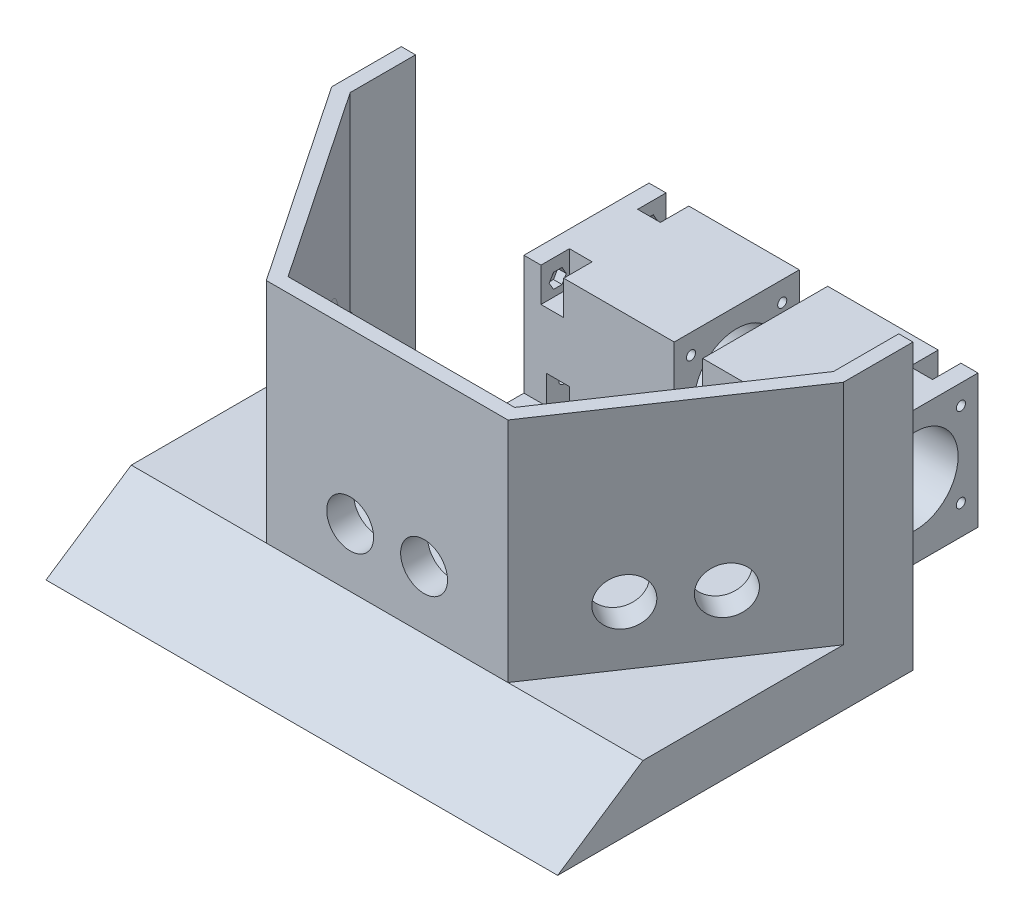
SolidWorks part; units mm, degrees
other "Markup1"
sketch "Sketch35"
ref_plane "Front Plane" through (0, 0, 0) normal (0, 0, 1) x (1, 0, 0)
ref_plane "Top Plane" through (0, 0, 0) normal (0, 1, 0) x (1, 0, 0)
ref_plane "Right Plane" through (0, 0, 0) normal (1, 0, 0) x (0, 0, -1)
sketch "Sketch1" plane through (0, 0, 0) normal (0, 0, 1) x (1, 0, 0)
  line L1 (-76.9072, 53.1245) -> (103.0928, 53.1245)
  line L2 (-76.9072, 53.1245) -> (-76.9072, -46.8755)
  line L3 (-76.9072, -46.8755) -> (103.0928, -46.8755)
  line L4 (103.0928, 53.1245) -> (103.0928, -46.8755)
  dimension "D1" = 180
  dimension "D2" = 100
extrude "Boss-Extrude1" add sketch "Sketch1" along normal blind 150
sketch "Sketch2" plane through (0, 53.1245, 0) normal (0, 1, 0) x (1, 0, 0)
  line L0 (13.0928, 0) -> (13.0928, -150) construction
  line L4 (103.0928, 0) -> (-76.9072, 0) construction
  line L9 (103.0928, -150) -> (-76.9072, -150) construction
sketch "Sketch4" plane through (0, 53.1245, 0) normal (0, 1, 0) x (1, 0, 0)
  line L0 (-29.4072, -150) -> (55.5928, -150) construction
  line L1 (-76.9072, 0) -> (-76.9072, -79.5106) construction
  line L3 (-76.9072, -150) -> (-76.9072, 0) construction
  line L5 (-76.9072, -79.5106) -> (-29.4072, -150) construction
  line L6 (13.0928, 0) -> (13.0928, -150) construction
  line L8 (103.0928, -150) -> (-76.9072, -150) construction
  line L9 (103.0928, 0) -> (103.0928, -79.5106) construction
  line L10 (103.0928, -150) -> (103.0928, 0) construction
  line L11 (103.0928, -79.5106) -> (55.5928, -150) construction
  line L13 (-76.9072, -79.5106) -> (-29.4072, -150)
  line L14 (-29.4072, -150) -> (-76.9072, -150)
  line L15 (-76.9072, -150) -> (-76.9072, -79.5106)
  line L16 (55.5928, -150) -> (103.0928, -150)
  line L17 (103.0928, -150) -> (103.0928, -79.5106)
  line L18 (103.0928, -79.5106) -> (55.5928, -150)
  line M6 (-76.9072, 0) -> (-76.9072, -150)
  line M7 (-76.9072, -150) -> (103.0928, -150)
  line M8 (103.0928, -150) -> (103.0928, 0)
  dimension "D1" = 85
  dimension "D2" = 47.5
  dimension "D3" = 47.5
  dimension "D4" = 85
  dimension "D5" = 79.5106
extrude "Cut-Extrude2" cut sketch "Sketch4" against normal blind 80 contours M8 M7 | M6 M7 region at (87.2595, 53.1245, 126.5035) region at (-61.0739, 53.1245, 126.5035)
shell "Shell1" thickness 5 removed face at (13.0928, 53.1245, 76.5035)
sketch "Sketch6" plane through (103.0928, 0, 0) normal (1, 0, 0) x (0, 0, -1)
  line L0 (-150, -26.8755) -> (-150, -46.8755)
  line L1 (-150, -46.8755) -> (-180, -46.8755)
  line L2 (-180, -46.8755) -> (-150, -26.8755)
  dimension "D1" = 30
  dimension "D2" = 36.0555
extrude "Boss-Extrude2" add sketch "Sketch6" against normal blind 180 contours L2 L0 L1
sketch "Sketch26" plane through (0, 0, 0) normal (0, 0, -1) x (-1, 0, 0)
  line L0 (76.9072, 53.1245) -> (76.9072, -46.8755) construction
  line L1 (-103.0928, 53.1245) -> (76.9072, 53.1245)
  line L2 (-103.0928, 53.1245) -> (-103.0928, -41.8755)
  line L3 (-103.0928, -41.8755) -> (76.9072, -41.8755)
  line L4 (76.9072, 53.1245) -> (76.9072, -41.8755)
  dimension "D1" = 95
extrude "Cut-Extrude10" cut sketch "Sketch26" against normal blind 5
sketch "Sketch27" plane through (103.0928, 0, 0) normal (1, 0, 0) x (0, 0, -1)
  line L1 (-5, 53.1245) -> (-55, 53.1245)
  line L2 (-5, 53.1245) -> (-5, -41.8755)
  line L3 (-5, -41.8755) -> (-55, -41.8755)
  line L4 (-55, 53.1245) -> (-55, -41.8755)
  dimension "D1" = 50
  dimension "D2" = 95
extrude "Cut-Extrude11" cut sketch "Sketch27" against normal through all
sketch3d "3DSketch1" plane through (0, 0, 0) normal (0, 0, 1) x (1, 0, 0)
sketch "Sketch28" plane through (-89.7376, 0, 60.4706) normal (-0.8293, 0, 0.5588) x (0.5588, 0, 0.8293)
  line L0 (22.9595, -26.8755) -> (107.9595, -26.8755) construction
  line L1 (107.9595, -26.8755) -> (107.9595, 53.1245) construction
  line L2 (22.9595, -26.8755) -> (22.9595, 53.1245) construction
  circle A0 centre (52.4595, -6.2755) radius 8.25
  circle A1 centre (78.4595, -6.2755) radius 8.25
  dimension "D1" = 16.5
  dimension "D2" = 16.5
  dimension "D3" = 26
  dimension "D4" = 20.6
  dimension "D5" = 29.5
  dimension "D6" = 29.5
extrude "Cut-Extrude12" cut sketch "Sketch28" against normal blind 82
sketch "Sketch29" plane through (107.7458, 0, 72.6056) normal (0.8293, 0, 0.5588) x (0.5588, 0, -0.8293)
  line L0 (-8.3264, -26.8755) -> (-8.3264, 53.1245) construction
  line L2 (-8.3264, -26.8755) -> (-93.3264, -26.8755) construction
  circle A0 centre (-63.8264, -6.2755) radius 8.25
  circle A1 centre (-37.8264, -6.2755) radius 8.25
  dimension "D1" = 16.5
  dimension "D2" = 16.5
  dimension "D3" = 26
  dimension "D4" = 29.5
  dimension "D5" = 20.6
  dimension "D6" = 20.6
extrude "Cut-Extrude13" cut sketch "Sketch29" against normal blind 82
sketch "Sketch30" plane through (0, 0, 150) normal (0, 0, 1) x (1, 0, 0)
  line L0 (-29.4072, -26.8755) -> (55.5928, -26.8755) construction
  line L1 (55.5928, -26.8755) -> (55.5928, 53.1245) construction
  line L2 (-29.4072, -26.8755) -> (-29.4072, 53.1245) construction
  circle A0 centre (0.0928, -6.2755) radius 8.25
  circle A1 centre (26.0928, -6.2755) radius 8.25
  dimension "D1" = 16.5
  dimension "D2" = 16.5
  dimension "D4" = 20.6
  dimension "D3" = 26
  dimension "D5" = 20.6
  dimension "D6" = 29.5
  dimension "D7" = 29.5
extrude "Cut-Extrude14" cut sketch "Sketch30" against normal blind 82 contours A0 | A1
sketch "Sketch31" plane through (103.5994, 0, 69.8115) normal (-0.8293, 0, -0.5588) x (-0.5588, 0, 0.8293)
  circle A1 centre (63.8264, -6.2755) radius 10.25
  circle A2 centre (63.8264, -6.2755) radius 8.25 construction
  circle A3 centre (37.8264, -6.2755) radius 10.25
  circle A4 centre (37.8264, -6.2755) radius 8.25 construction
  circle A5 centre (63.8264, -6.2755) radius 8.25
  circle A6 centre (37.8264, -6.2755) radius 8.25
  dimension "D1" = 2
  dimension "D2" = 2
extrude "Boss-Extrude4" add sketch "Sketch31" along normal blind 4.5
sketch "Sketch33" plane through (0, 0, 145) normal (0, 0, -1) x (-1, 0, 0)
  circle A0 centre (-26.0928, -6.2755) radius 8.25
  circle A1 centre (-26.0928, -6.2755) radius 10.25
  circle A2 centre (-0.0928, -6.2755) radius 8.25
  circle A3 centre (-0.0928, -6.2755) radius 10.25
  dimension "D1" = 2
  dimension "D2" = 2
extrude "Boss-Extrude5" add sketch "Sketch33" along normal blind 4.5
sketch "Sketch34" plane through (-85.5911, 0, 57.6765) normal (0.8293, 0, -0.5588) x (-0.5588, 0, -0.8293)
  circle A0 centre (-78.4595, -6.2755) radius 8.25
  circle A1 centre (-52.4595, -6.2755) radius 8.25
  circle A2 centre (-78.4595, -6.2755) radius 10.25
  circle A3 centre (-52.4595, -6.2755) radius 10.25
  dimension "D1" = 2
  dimension "D2" = 2
extrude "Boss-Extrude6" add sketch "Sketch34" along normal blind 4.5
fillet "Fillet1" radius 3 6 edges at (-50.5475, -6.2755, 109.6807) (-36.0181, -6.2755, 131.2421) (10.3428, -6.2755, 145) (36.3428, -6.2755, 145) (76.7331, -6.2755, 109.6807) (62.2037, -6.2755, 131.2421)
sketch "Sketch68" plane through (0, -41.8755, 0) normal (0, 1, 0) x (1, 0, 0)
  line L0 (-54.5072, -131.3) -> (-61.9072, -138.7) construction
  line L1 (-61.9072, -131.3) -> (-54.5072, -131.3)
  line L2 (-61.9072, -131.3) -> (-61.9072, -138.7)
  line L3 (-61.9072, -138.7) -> (-54.5072, -138.7)
  line L4 (-54.5072, -131.3) -> (-54.5072, -138.7)
  line L5 (-76.9072, -180) -> (103.0928, -180) construction
  line L6 (-76.9072, -180) -> (-76.9072, 0) construction
  line L7 (13.0928, -145) -> (13.0928, -117.6017) construction
  line L8 (-71.9072, -145) -> (98.0928, -145) construction
  line L9 (13.0928, 0) -> (13.0928, -150) construction
  line L10 (80.6928, -131.3) -> (88.0928, -138.7) construction
  line L11 (80.6928, -131.3) -> (80.6928, -138.7)
  line L12 (88.0928, -138.7) -> (80.6928, -138.7)
  line L13 (88.0928, -131.3) -> (88.0928, -138.7)
  line L14 (88.0928, -131.3) -> (80.6928, -131.3)
  point P4 (-58.2072, -135)
  dimension "D1" = 7.4
  dimension "D2" = 7.4
  dimension "D3" = 45
  dimension "D4" = 15
extrude "Cut-Extrude40" cut sketch "Sketch68" against normal blind 26
sketch "Sketch69" plane through (0, -41.8755, 0) normal (0, 1, 0) x (1, 0, 0)
  line L0 (-58.2072, -131.3) -> (-58.2072, -123.2) construction
  line L1 (-54.5072, -131.3) -> (-61.9072, -131.3) construction
  line L2 (13.0928, -180) -> (13.0928, -157.8617) construction
  line L3 (-76.9072, -180) -> (103.0928, -180) construction
  line L4 (84.3928, -131.3) -> (84.3928, -123.2) construction
  circle A0 centre (-58.2072, -123.2) radius 1.65
  circle A1 centre (84.3928, -123.2) radius 1.65
  dimension "D1" = 3.3
  dimension "D2" = 8.1
extrude "Cut-Extrude41" cut sketch "Sketch69" against normal blind 26
sketch "Sketch70" plane through (0, -46.8755, 0) normal (0, -1, 0) x (1, 0, 0)
  circle A0 centre (84.3928, 123.2) radius 4
  circle A1 centre (-58.2072, 123.2) radius 4
  dimension "D1" = 8
  dimension "D2" = 8
extrude "Cut-Extrude43" cut sketch "Sketch70" against normal blind 3
sketch "Sketch36" plane through (0, -41.8755, 0) normal (0, 1, 0) x (1, 0, 0)
  line L0 (13.0928, 0) -> (8.0928, 0) construction
  line L1 (103.0928, 0) -> (-76.9072, 0) construction
  line L2 (13.0928, 0) -> (18.0928, 0) construction
  line L3 (13.0928, -150) -> (13.0928, -80.1183) construction
  line L8 (13.0928, 0) -> (13.0928, -150) construction
  line L9 (18.0928, 0) -> (70.9628, 0) construction
  line L14 (8.0928, -44) -> (-44.7772, -44)
  line L15 (18.0928, 0) -> (70.9628, 0)
  line L16 (18.0928, 0) -> (18.0928, -44)
  line L17 (18.0928, -44) -> (70.9628, -44)
  line L18 (70.9628, 0) -> (70.9628, -44)
  line L19 (-44.7772, 0) -> (-44.7772, -44)
  line L20 (8.0928, 0) -> (-44.7772, 0)
  line L21 (8.0928, 0) -> (8.0928, -44)
  dimension "D1" = 44
  dimension "D2" = 5
  dimension "D5" = 52.87
extrude "Boss-Extrude7" add sketch "Sketch36" along normal blind 42 contours L17 L18 L15 L16 | L14 L19 L20 L21
sketch "Sketch72" plane through (0, -41.8755, 0) normal (0, 1, 0) x (1, 0, 0)
  line L0 (13.0928, -150) -> (13.0928, -110.5101) construction
  line L1 (103.0928, -55) -> (70.9628, -55)
  line L2 (103.0928, -55) -> (103.0928, 0)
  line L3 (103.0928, 0) -> (70.9628, 0)
  line L4 (70.9628, -55) -> (70.9628, 0)
  line L5 (13.0928, 0) -> (13.0928, -150) construction
  line L6 (-76.9072, 0) -> (-44.7772, 0)
  line L7 (-44.7772, -55) -> (-44.7772, 0)
  line L8 (-76.9072, -55) -> (-44.7772, -55)
  line L9 (-76.9072, -55) -> (-76.9072, 0)
  line M12 (-44.7772, -44) -> (-44.7772, 0)
  line M13 (-44.7772, 0) -> (-76.9072, 0)
  line M14 (-76.9072, 0) -> (-76.9072, -55)
  line M15 (-76.9072, -55) -> (-71.9072, -55)
extrude "Cut-Extrude44" cut sketch "Sketch72" against normal blind 42 contours L8 L7 M15 M12 M13 M14 | L2 L1 L4 L3 region at (-60.8422, -41.8755, 27.5)
sketch "Sketch73" plane through (70.9628, 0, 0) normal (1, 0, 0) x (0, 0, -1)
  line L0 (-42.1, -1.6755) -> (-1.9, -1.6755) construction
  line L1 (-1.9, -1.6755) -> (-1.9, -41.8755) construction
  line L2 (-1.9, -41.8755) -> (-42.1, -41.8755) construction
  line L3 (-42.1, -41.8755) -> (-42.1, -1.6755) construction
  line L4 (0, 0.1245) -> (0, -46.8755) construction
  line L5 (-44, 0.1245) -> (-44, -41.8755) construction
  line L6 (-42.1, -21.7755) -> (-1.9, -21.7755) construction
  line L7 (-22, -41.8755) -> (-22, -1.6755) construction
  line L9 (-55, -46.8755) -> (0, -46.8755) construction
  circle A0 centre (-38.1, -6.8755) radius 1.6
  circle A4 centre (-6, -6.8755) radius 1.6
  circle A5 centre (-38.1, -36.4755) radius 1.6
  circle A7 centre (-6.05, -36.4755) radius 1.6
  circle A8 centre (-22, -21.7755) radius 15
  dimension "D5" = 3.2
  dimension "D8" = 3.2
  dimension "D11" = 3.2
  dimension "D12" = 3.2
  dimension "D17" = 30
  dimension "D1" = 40.2
  dimension "D2" = 1.9
  dimension "D3" = 1.9
  dimension "D4" = 5
  dimension "D6" = 5.2
  dimension "D7" = 4
  dimension "D9" = 5.2
  dimension "D10" = 4.1
  dimension "D13" = 5.4
  dimension "D14" = 4
  dimension "D15" = 5.4
  dimension "D16" = 4.15
extrude "Cut-Extrude45" cut sketch "Sketch73" against normal blind 149 contours A4 | A5 | A7 | A0 | A8 region at (70.9628, -6.8755, 6) region at (70.9628, -36.4755, 38.1)
sketch "Sketch77" plane through (0, 0.1245, 0) normal (0, 1, 0) x (1, 0, 0)
  line L0 (18.0928, -44) -> (70.9628, -44) construction
  line L1 (64.9628, -44) -> (56.9628, -44)
  line L2 (64.9628, -44) -> (64.9628, -34)
  line L3 (64.9628, -34) -> (56.9628, -34)
  line L4 (56.9628, -44) -> (56.9628, -34)
  line L10 (18.0928, 0) -> (70.9628, 0) construction
  line L16 (56.9628, 0) -> (64.9628, 0)
  line L17 (56.9628, 0) -> (56.9628, -10)
  line L18 (56.9628, -10) -> (64.9628, -10)
  line L19 (64.9628, 0) -> (64.9628, -10)
  line L20 (70.9628, 0) -> (70.9628, -44) construction
  line L21 (13.0928, 0) -> (13.0928, -65.0172) construction
  line L22 (13.0928, 0) -> (13.0928, -150) construction
  line L23 (-30.7772, -10) -> (-38.7772, -10)
  line L24 (-38.7772, 0) -> (-38.7772, -10)
  line L25 (-30.7772, 0) -> (-38.7772, 0)
  line L26 (-30.7772, 0) -> (-30.7772, -10)
  line L27 (-38.7772, -34) -> (-30.7772, -34)
  line L28 (-30.7772, -44) -> (-30.7772, -34)
  line L29 (-38.7772, -44) -> (-30.7772, -44)
  line L30 (-38.7772, -44) -> (-38.7772, -34)
  dimension "D1" = 10
  dimension "D2" = 6
  dimension "D3" = 10
  dimension "D4" = 6
  dimension "D7" = 8
  dimension "D8" = 8
extrude "Cut-Extrude46" cut sketch "Sketch77" against normal blind 12
sketch "Sketch78" plane through (0, -46.8755, 0) normal (0, -1, 0) x (1, 0, 0)
  line L0 (70.9628, 0) -> (70.9628, 44.078) construction
  line L2 (70.9628, 55) -> (70.9628, 0) construction
  dimension "D1" = 44.078
sketch "Sketch80" plane through (64.9628, 0, 0) normal (-1, 0, 0) x (0, 0, 1)
  line L0 (10, -11.8755) -> (0, -11.8755) construction
  line L7 (4.6725, -4.1778) -> (3, -6.6763)
  line L8 (3, -6.6763) -> (4.3275, -9.374)
  line L9 (4.3275, -9.374) -> (7.3275, -9.5732)
  line L10 (7.3275, -9.5732) -> (9, -7.0747)
  line L11 (9, -7.0747) -> (7.6725, -4.3771)
  line L12 (7.6725, -4.3771) -> (4.6725, -4.1778)
  circle A0 centre (6, -6.8755) radius 2.6038 construction
  dimension "D3" = 5.2076
  dimension "D1" = 6
  dimension "D2" = 5
extrude "Cut-Extrude47" cut sketch "Sketch80" against normal blind 3
sketch "Sketch81" plane through (64.9628, 0, 0) normal (-1, 0, 0) x (0, 0, 1)
  line L1 (41.1, -6.8755) -> (39.6, -4.2774)
  line L2 (39.6, -4.2774) -> (36.6, -4.2774)
  line L3 (36.6, -4.2774) -> (35.1, -6.8755)
  line L4 (35.1, -6.8755) -> (36.6, -9.4736)
  line L5 (36.6, -9.4736) -> (39.6, -9.4736)
  line L6 (39.6, -9.4736) -> (41.1, -6.8755)
  circle A0 centre (38.1, -6.8755) radius 2.5981 construction
  dimension "D2" = 5.1962
  dimension "D1" = 6
extrude "Cut-Extrude48" cut sketch "Sketch81" against normal blind 3
sketch "Sketch82" plane through (-38.7772, 0, 0) normal (1, 0, 0) x (0, 0, -1)
  line L1 (-3, -6.8755) -> (-4.5, -4.2774)
  line L2 (-4.5, -4.2774) -> (-7.5, -4.2774)
  line L3 (-7.5, -4.2774) -> (-9, -6.8755)
  line L4 (-9, -6.8755) -> (-7.5, -9.4736)
  line L5 (-7.5, -9.4736) -> (-4.5, -9.4736)
  line L6 (-4.5, -9.4736) -> (-3, -6.8755)
  circle A0 centre (-6, -6.8755) radius 2.5981 construction
  dimension "D1" = 6
extrude "Cut-Extrude49" cut sketch "Sketch82" against normal blind 3
sketch "Sketch83" plane through (-38.7772, 0, 0) normal (1, 0, 0) x (0, 0, -1)
  line L1 (-35.1, -6.8755) -> (-36.6, -4.2774)
  line L2 (-36.6, -4.2774) -> (-39.6, -4.2774)
  line L3 (-39.6, -4.2774) -> (-41.1, -6.8755)
  line L4 (-41.1, -6.8755) -> (-39.6, -9.4736)
  line L5 (-39.6, -9.4736) -> (-36.6, -9.4736)
  line L6 (-36.6, -9.4736) -> (-35.1, -6.8755)
  circle A0 centre (-38.1, -6.8755) radius 2.5981 construction
  dimension "D1" = 6
extrude "Cut-Extrude50" cut sketch "Sketch83" against normal blind 3
sketch "Sketch84" plane through (0, -46.8755, 0) normal (0, -1, 0) x (1, 0, 0)
  line L0 (-44.7772, 0) -> (70.9628, 0) construction
  line L1 (62.9628, 0) -> (54.9628, 0)
  line L2 (62.9628, 0) -> (62.9628, 10)
  line L3 (62.9628, 10) -> (54.9628, 10)
  line L4 (54.9628, 0) -> (54.9628, 10)
  line L5 (70.9628, 0) -> (70.9628, 44.078) construction
  line L10 (103.0928, 55) -> (70.9628, 55) construction
  line L11 (13.0928, 0) -> (13.0928, 36.7218) construction
  line L12 (62.9628, 44) -> (54.9628, 44)
  line L13 (62.9628, 44) -> (62.9628, 34)
  line L14 (62.9628, 34) -> (54.9628, 34)
  line L15 (54.9628, 44) -> (54.9628, 34)
  line L16 (13.0928, 0) -> (13.0928, 150) construction
  line L17 (-36.7772, 34) -> (-28.7772, 34)
  line L18 (-28.7772, 44) -> (-28.7772, 34)
  line L19 (-36.7772, 44) -> (-28.7772, 44)
  line L20 (-36.7772, 44) -> (-36.7772, 34)
  line L21 (-36.7772, 10) -> (-28.7772, 10)
  line L22 (-28.7772, 0) -> (-28.7772, 10)
  line L23 (-36.7772, 0) -> (-28.7772, 0)
  line L24 (-36.7772, 0) -> (-36.7772, 10)
  dimension "D1" = 10
  dimension "D2" = 8
  dimension "D3" = 8
  dimension "D4" = 8
  dimension "D5" = 10
  dimension "D6" = 8
  dimension "D7" = 11
extrude "Cut-Extrude51" cut sketch "Sketch84" against normal blind 15
